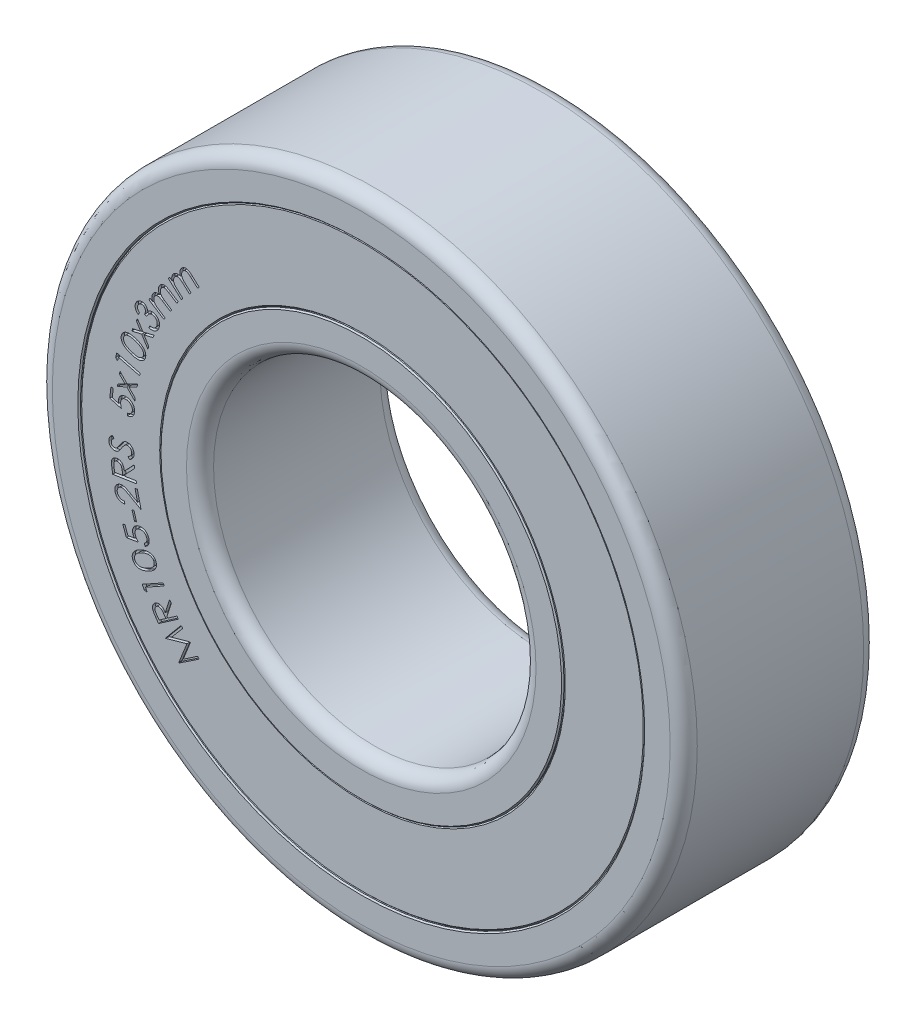
SolidWorks part; units mm, degrees
material "AISI 316 Annealed Stainless Steel Bar (SS)"
ref_plane "Front" through (0, 0, 0) normal (0, 0, 1) x (1, 0, 0)
ref_plane "Top" through (0, 0, 0) normal (0, 1, 0) x (1, 0, 0)
ref_plane "Right" through (0, 0, 0) normal (1, 0, 0) x (0, 0, -1)
sketch "LAYOUT R" plane through (0, 0, 0) normal (1, 0, 0) x (0, 0, -1)
  line L0 (-1.5, 2.5) -> (1.5, 2.5)
  line L1 (1.5, -5) -> (-1.5, -5) construction
  line L2 (1.5, -5) -> (1.5, 5) construction
  line L3 (1.5, 5) -> (-1.5, 5)
  line L4 (-1.5, -5) -> (-1.5, 5) construction
  line L5 (1.5, -5) -> (-1.5, 5) construction
  line L6 (1.5, 5) -> (-1.5, -5) construction
  line L7 (-1.5, 3.125) -> (1.5, 3.125)
  line L8 (-1.5, 4.375) -> (1.5, 4.375)
  line L11 (-17.5, 0) -> (17.5, 0) construction
  line L12 (-1.5, 5) -> (-1.5, 4.375)
  line L13 (1.5, 5) -> (1.5, 4.375)
  line L14 (-1.5, 4.375) -> (-1.5, 3.125)
  line L15 (1.5, 4.375) -> (1.5, 3.125)
  line L16 (-1.5, 3.125) -> (-1.5, 2.5)
  line L17 (1.5, 3.125) -> (1.5, 2.5)
  line L18 (-1.48, 4.375) -> (-1.48, 3.125)
  line L19 (1.48, 4.375) -> (1.48, 3.125)
  point P0 (0, 0)
  point P15 (0, 0)
  dimension "D1" = 3
  dimension "D2" = 10
  dimension "D3" = 2.5
  dimension "D6" = 0.02
  dimension "D7" = 0.02
  dimension "D4" = 3.125
  dimension "D5" = 4.375
sketch "Sketch R, INNER BODY" plane through (0, 0, 0) normal (1, 0, 0) x (0, 0, -1)
  line L0 (-1.5, 2.5) -> (1.5, 2.5) construction
  line L2 (-1.5, 3.125) -> (1.5, 3.125) construction
  line L4 (-1.5, 2.5) -> (1.5, 2.5)
  line L6 (-1.5, 3.125) -> (1.5, 3.125)
  line L8 (1.5, 3.125) -> (1.5, 2.5) construction
  line L9 (-1.5, 3.125) -> (-1.5, 2.5) construction
  line L10 (1.5, 3.125) -> (1.5, 2.5)
  line L11 (-1.5, 3.125) -> (-1.5, 2.5)
  line L12 (-17.5, 0) -> (17.5, 0) construction
  line L13 (-17.5, 0) -> (17.5, 0) construction
sketch "Sketch R, OUTER BODY" plane through (0, 0, 0) normal (1, 0, 0) x (0, 0, -1)
  line L2 (-1.5, 4.375) -> (1.5, 4.375) construction
  line L3 (1.5, 5) -> (-1.5, 5) construction
  line L6 (-1.5, 4.375) -> (1.5, 4.375)
  line L7 (1.5, 5) -> (-1.5, 5)
  line L8 (-17.5, 0) -> (17.5, 0) construction
  line L9 (-17.5, 0) -> (17.5, 0) construction
  line L10 (1.5, 5) -> (1.5, 4.375) construction
  line L11 (-1.5, 5) -> (-1.5, 4.375) construction
  line L12 (1.5, 5) -> (1.5, 4.375)
  line L13 (-1.5, 5) -> (-1.5, 4.375)
sketch "Sketch R, SEAL FACES" plane through (0, 0, 0) normal (1, 0, 0) x (0, 0, -1)
  line L0 (-17.5, 0) -> (17.5, 0) construction
  line L1 (-17.5, 0) -> (17.5, 0) construction
  line L3 (-1.5, 3.125) -> (1.5, 3.125) construction
  line L5 (-1.5, 4.375) -> (1.5, 4.375) construction
  line L7 (-1.48, 3.125) -> (1.48, 3.125)
  line L9 (-1.48, 4.375) -> (1.48, 4.375)
  line L10 (1.48, 4.375) -> (1.48, 3.125) construction
  line L11 (-1.48, 4.375) -> (-1.48, 3.125) construction
  line L12 (1.48, 4.375) -> (1.48, 3.125)
  line L13 (-1.48, 4.375) -> (-1.48, 3.125)
revolve "Revolve INNER BODY" add sketch "Sketch R, INNER BODY" angle 360 about L13
fillet "Fillet INNER BODY" radius 0.21 2 edges at (2.5, 0, 1.5) (2.5, 0, -1.5)
chamfer "Chamfer INNER BODY" distance 0.02 angle 45 2 edges at (3.125, 0, -1.5) (3.125, 0, 1.5)
revolve "Revolve OUTER BODY" add sketch "Sketch R, OUTER BODY" angle 360 about L9
fillet "Fillet OUTER BODY" radius 0.21 2 edges at (5, 0, -1.5) (5, 0, 1.5)
chamfer "Chamfer OUTER BODY" distance 0.02 angle 45 2 edges at (4.375, 0, 1.5) (4.375, 0, -1.5)
revolve "Revolve SEALS" add sketch "Sketch R, SEAL FACES" angle 360 about L1
chamfer "Chamfer SEALS" distance 0.02 angle 45 4 edges at (3.125, 0, -1.48) (4.375, 0, -1.48) (4.375, 0, 1.48) (3.125, 0, 1.48)
sketch "Sketch TEXT RADIUS 1 — MANUALLY ASSIGN TEXT AND FONT SIZE (FROM EQUATIONS)" plane through (0, 0, 1.48) normal (0, 0, 1) x (1, 0, 0)
  circle A0 centre (0, 0) radius 3.5625 construction
  text T0 "MR105-2RS  5x10x3mm" font "Century Gothic" height 0.375
  dimension "D1" = 7.125
extrude "Cut-Extrude SEAL LABEL 1" cut sketch "Sketch TEXT RADIUS 1 — MANUALLY ASSIGN TEXT AND FONT SIZE (FROM EQUATIONS)" against normal blind 0.05
sketch "Sketch TEXT RADIUS 2 — MANUALLY ASSIGN TEXT AND FONT SIZE (FROM EQUATIONS)" plane through (0, 0, -1.48) normal (0, 0, -1) x (-1, 0, 0)
  circle A0 centre (0, 0) radius 3.5625 construction
  text T0 "MR105-2RS  5x10x3mm" font "Century Gothic" height 0.375
  dimension "D1" = 7.125
extrude "Cut-Extrude SEAL LABEL 2" cut sketch "Sketch TEXT RADIUS 2 — MANUALLY ASSIGN TEXT AND FONT SIZE (FROM EQUATIONS)" against normal blind 0.05
equation "\"_i__BORE\"= 5"
equation "\"_i__OUTSIDE_DIAMETER\"= 10"
equation "\"_i__WIDTH\"= 3"
equation "\"_i_optional__TEXT_RADIUS_ADJUSTMENT\"= 0"
equation "\"_output__FONT_SIZE_mm\"= \"BODY_SPAN__SEAL__OF_RADIUS\" * \"param__FONT_SIZE_RATIO\"'MANUALLY ASSIGN TO FONT"
equation "\"BODY__HALF_WIDTH\"= \"_i__WIDTH\" / 2"
equation "\"BODY_SPAN___OF_DIAMETER\"= \"_i__OUTSIDE_DIAMETER\" - \"_i__BORE\""
equation "\"BODY_SPAN___OF_RADIUS\"= \"BODY_SPAN___OF_DIAMETER\" / 2"
equation "\"BODY_SPAN__BORE_AND_OD__OF RADIUS\"= ( \"BODY_SPAN___OF_RADIUS\" - \"BODY_SPAN__SEAL__OF_RADIUS\" ) / 2"
equation "\"BODY_SPAN__SEAL__OF_RADIUS\"= \"BODY_SPAN___OF_RADIUS\" * \"param__SEAL_PANEL_SPAN__RATIO_OF_BODY_RADIAN\""
equation "\"BORE__RADIUS\"= \"_i__BORE\" / 2"
equation "\"CORNER_RADII\"= \"_i__WIDTH\" * \"param__CORNER_RADII__ISO_MAX_RATIO_TO_WIDTH\""
equation "\"param__CORNER_RADII__ISO_MAX_RATIO_TO_WIDTH\"= 0.07'WHERE WIDTH IS LESS THAN DIAMETER"
equation "\"param__FONT_SIZE_RATIO\"= 0.3"
equation "\"param__SEAL_FACE_INSET__RATIO_OF_WIDTH\"= .01"
equation "\"param__SEAL_PANEL_SPAN__RATIO_OF_BODY_RADIAN\"= 0.5"
equation "\"param__SIDE_CHAMFERS__RATIO_TO_OD\"= 1 / 500"
equation "\"RING_INNER__OUTSIDE_RADIUS\"= \"BORE__RADIUS\" + \"BODY_SPAN__BORE_AND_OD__OF RADIUS\""
equation "\"RING_OUTER__OUTSIDE_RADIUS\"= ( \"_i__OUTSIDE_DIAMETER\" / 2 ) - \"BODY_SPAN__BORE_AND_OD__OF RADIUS\""
equation "\"SEAL_FACE_INSET\"= \"_i__WIDTH\" * \"param__SEAL_FACE_INSET__RATIO_OF_WIDTH\""
equation "\"SIDE_FACE_AND_SEAL_CHAMFERS\"= \"_i__OUTSIDE_DIAMETER\" * \"param__SIDE_CHAMFERS__RATIO_TO_OD\""
equation "\"TEXT_RADIUS\"= \"_i__BORE\" + ( \"BODY_SPAN___OF_DIAMETER\" / 2 ) - \"_output__FONT_SIZE_mm\" + \"_i_optional__TEXT_RADIUS_ADJUSTMENT\""
equation "\"D1@Chamfer INNER BODY\"=\"SIDE_FACE_AND_SEAL_CHAMFERS\""
equation "\"D1@Chamfer OUTER BODY\"=\"SIDE_FACE_AND_SEAL_CHAMFERS\""
equation "\"D1@Chamfer SEALS\"=\"SIDE_FACE_AND_SEAL_CHAMFERS\""
equation "\"D1@Fillet INNER BODY\"=\"CORNER_RADII\""
equation "\"D1@Fillet OUTER BODY\"=\"CORNER_RADII\""
equation "\"D1@LAYOUT R\"=\"_i__WIDTH\""
equation "\"D1@Sketch TEXT RADIUS 1 — MANUALLY ASSIGN TEXT AND FONT SIZE (FROM EQUATIONS)\" = \"TEXT_RADIUS\""
equation "\"D1@Sketch TEXT RADIUS 2 — MANUALLY ASSIGN TEXT AND FONT SIZE (FROM EQUATIONS)\" = \"TEXT_RADIUS\""
equation "\"D2@LAYOUT R\"=\"_i__OUTSIDE_DIAMETER\""
equation "\"D3@LAYOUT R\"=\"BORE__RADIUS\""
equation "\"D4@LAYOUT R\"=\"RING_INNER__OUTSIDE_RADIUS\""
equation "\"D5@LAYOUT R\"=\"RING_OUTER__OUTSIDE_RADIUS\""
